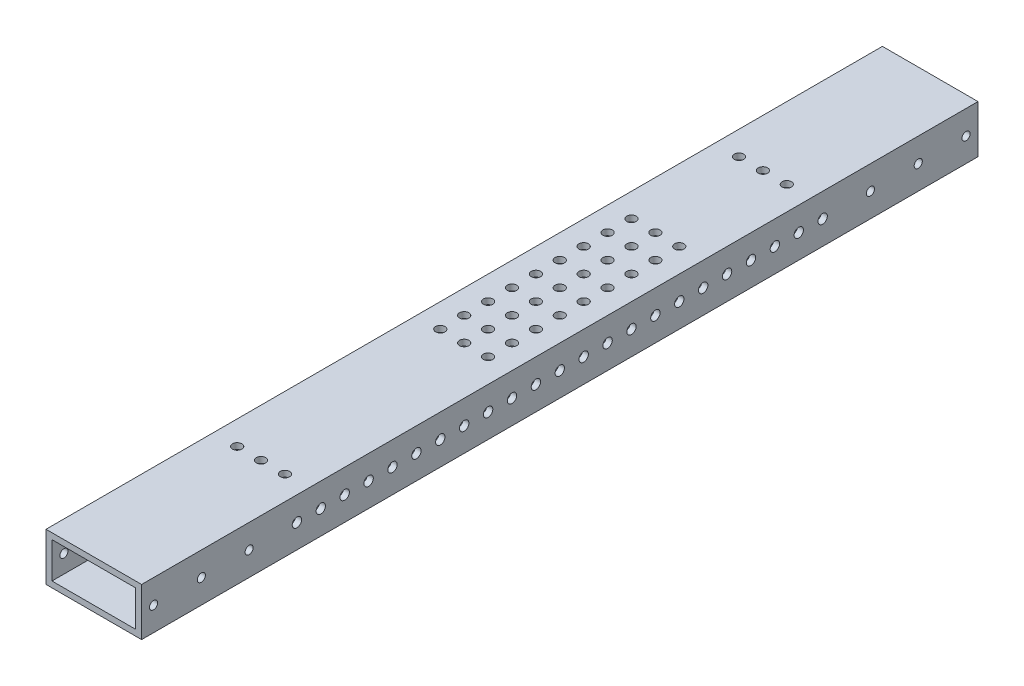
SolidWorks part; units mm, degrees
material "6061-T6 (SS)"
ref_plane "Front Plane" through (0, 0, 0) normal (0, 0, 1) x (1, 0, 0)
ref_plane "Top Plane" through (0, 0, 0) normal (0, 1, 0) x (1, 0, 0)
ref_plane "Right Plane" through (0, 0, 0) normal (1, 0, 0) x (0, 0, -1)
sketch "Sketch1" plane through (0, 0, 0) normal (0, 0, 1) x (1, 0, 0)
  line L0 (-22.225, 9.525) -> (22.225, 9.525)
  line L1 (-25.4, 12.7) -> (25.4, 12.7)
  line L2 (-25.4, 12.7) -> (-25.4, -12.7)
  line L3 (-25.4, -12.7) -> (25.4, -12.7)
  line L4 (25.4, 12.7) -> (25.4, -12.7)
  line L5 (22.225, 9.525) -> (22.225, -9.525)
  line L6 (-22.225, -9.525) -> (22.225, -9.525)
  line L7 (-22.225, 9.525) -> (-22.225, -9.525)
  line L8 (-25.4, 12.7) -> (25.4, -12.7) construction
  line L9 (25.4, 12.7) -> (-25.4, -12.7) construction
  point P5 (0, 0)
  dimension "D1" = 50.8
  dimension "D2" = 25.4
  dimension "D3" = 3.175
extrude "Boss-Extrude1" add sketch "Sketch1" along normal mid plane 444.5
sketch "Sketch3" plane through (25.4, 0, 0) normal (1, 0, 0) x (0, 0, -1)
  line L0 (-222.25, -12.7) -> (-222.25, 12.7) construction
  line L1 (-222.25, 12.7) -> (222.25, 12.7) construction
  line L2 (222.25, -12.7) -> (222.25, 12.7) construction
  circle A0 centre (-215.9, 0) radius 2.1527
  circle A1 centre (-190.5, 0) radius 2.1527
  circle A2 centre (-165.1, 0) radius 2.1527
  circle A3 centre (215.9, 0) radius 2.159
  circle A4 centre (190.5, 0) radius 2.159
  circle A5 centre (165.1, 0) radius 2.159
  dimension "D2" = 4.3053
  dimension "D9" = 4.318
  dimension "D1" = 6.35
  dimension "D3" = 12.7
  dimension "D4" = 31.75
  dimension "D5" = 12.7
  dimension "D6" = 57.15
  dimension "D7" = 12.7
  dimension "D8" = 6.35
  dimension "D10" = 12.7
  dimension "D11" = 31.75
  dimension "D12" = 57.15
  dimension "D13" = 12.7
  dimension "D14" = 12.7
extrude "Cut-Extrude2" cut sketch "Sketch3" against normal through all
sketch "Sketch4" plane through (25.4, 0, 0) normal (1, 0, 0) x (0, 0, -1)
  line L1 (-222.25, -12.7) -> (-222.25, 12.7) construction
  line L2 (-222.25, -12.7) -> (222.25, -12.7) construction
  circle A2 centre (-215.9, 0) radius 2.4892 construction
  circle A3 centre (-203.2, 0) radius 2.4892 construction
  circle A16 centre (-190.5, 0) radius 2.4892 construction
  circle A17 centre (-177.8, 0) radius 2.4892 construction
  circle A18 centre (-165.1, 0) radius 2.4892 construction
  circle A35 centre (-152.4, 0) radius 2.4892
  circle A36 centre (-139.7, 0) radius 2.4892
  circle A37 centre (-127, 0) radius 2.4892
  circle A38 centre (-114.3, 0) radius 2.4892
  circle A39 centre (-101.6, 0) radius 2.4892
  circle A40 centre (-88.9, 0) radius 2.4892
  circle A41 centre (-76.2, 0) radius 2.4892
  circle A42 centre (-63.5, 0) radius 2.4892
  circle A43 centre (-50.8, 0) radius 2.4892
  circle A44 centre (-38.1, 0) radius 2.4892
  circle A45 centre (-25.4, 0) radius 2.4892
  circle A46 centre (-12.7, 0) radius 2.4892
  circle A47 centre (0, 0) radius 2.4892
  circle A48 centre (12.7, 0) radius 2.4892
  circle A49 centre (25.4, 0) radius 2.4892
  circle A50 centre (38.1, 0) radius 2.4892
  circle A51 centre (50.8, 0) radius 2.4892
  circle A52 centre (63.5, 0) radius 2.4892
  circle A53 centre (76.2, 0) radius 2.4892
  circle A54 centre (88.9, 0) radius 2.4892
  circle A55 centre (101.6, 0) radius 2.4892
  circle A56 centre (114.3, 0) radius 2.4892
  circle A57 centre (127, 0) radius 2.4892
  circle A58 centre (139.7, 0) radius 2.4892
  circle A59 centre (152.4, 0) radius 2.4892
  circle A60 centre (165.1, 0) radius 2.4892 construction
  circle A61 centre (177.8, 0) radius 2.4892 construction
  circle A62 centre (190.5, 0) radius 2.4892 construction
  circle A63 centre (203.2, 0) radius 2.4892 construction
  dimension "D2" = 4.9784
  dimension "D1" = 6.35
  dimension "D3" = 12.7
  dimension "D4" = 12.7
  dimension "D5" = 34
extrude "Cut-Extrude3" cut sketch "Sketch4" against normal through all contours A36 | A37 | A38 | A39 | A40 | A41 | A42 | A43 | A44 | A45 | A46 | A47 | A48 | A49 | A50 | A51 | A52 | A53 | A54 | A55 | A56 | A57 | A58 region at (25.4, 0, 139.7) region at (25.4, 0, 127) region at (25.4, 0, 114.3) region at (25.4, 0, 101.6) region at (25.4, 0, 88.9) region at (25.4, 0, 76.2) region at (25.4, 0, 63.5) region at (25.4, 0, 50.8) region at (25.4, 0, 38.1) region at (25.4, 0, 25.4) region at (25.4, 0, 12.7) region at (25.4, 0, 0) region at (25.4, 0, -12.7) region at (25.4, 0, -25.4) region at (25.4, 0, -38.1) region at (25.4, 0, -50.8) region at (25.4, 0, -63.5) region at (25.4, 0, -76.2) region at (25.4, 0, -88.9) region at (25.4, 0, -101.6) region at (25.4, 0, -114.3) region at (25.4, 0, -127) region at (25.4, 0, -139.7)
sketch "Sketch5" plane through (0, -12.7, 0) normal (0, -1, 0) x (1, 0, 0)
  line L0 (-25.4, 0) -> (25.4, 0) construction
  line L4 (25.4, 222.25) -> (25.4, -222.25) construction
  line L5 (-25.4, 222.25) -> (-25.4, -222.25) construction
  line L6 (-25.4, 222.25) -> (25.4, 222.25) construction
  circle A0 centre (-12.7, 133.35) radius 2.4892
  circle A1 centre (0, 133.35) radius 2.4892
  circle A2 centre (12.7, 133.35) radius 2.4892
  circle A3 centre (12.7, -133.35) radius 2.4892
  circle A4 centre (0, -133.35) radius 2.4892
  circle A5 centre (-12.7, -133.35) radius 2.4892
  circle A6 centre (-12.7, 25.4) radius 2.4892
  circle A7 centre (0, 25.4) radius 2.4892
  circle A8 centre (12.7, 25.4) radius 2.4892
  circle A9 centre (12.7, 12.7) radius 2.4892
  circle A10 centre (0, 12.7) radius 2.4892
  circle A11 centre (-12.7, 12.7) radius 2.4892
  circle A12 centre (12.7, 0) radius 2.4892
  circle A13 centre (0, 0) radius 2.4892
  circle A14 centre (-12.7, 0) radius 2.4892
  circle A15 centre (12.7, -12.7) radius 2.4892
  circle A16 centre (0, -12.7) radius 2.4892
  circle A17 centre (-12.7, -12.7) radius 2.4892
  circle A18 centre (12.7, -25.4) radius 2.4892
  circle A19 centre (0, -25.4) radius 2.4892
  circle A20 centre (-12.7, -25.4) radius 2.4892
  circle A21 centre (12.7, -38.1) radius 2.4892
  circle A22 centre (0, -38.1) radius 2.4892
  circle A23 centre (-12.7, -38.1) radius 2.4892
  circle A24 centre (12.7, -50.8) radius 2.4892
  circle A25 centre (0, -50.8) radius 2.4892
  circle A26 centre (-12.7, -50.8) radius 2.4892
  circle A27 centre (12.7, -63.5) radius 2.4892
  circle A28 centre (0, -63.5) radius 2.4892
  circle A29 centre (-12.7, -63.5) radius 2.4892
  circle A30 centre (12.7, -76.2) radius 2.4892
  circle A31 centre (0, -76.2) radius 2.4892
  circle A32 centre (-12.7, -76.2) radius 2.4892
  dimension "D1" = 4.9784
  dimension "D3" = 12.7
  dimension "D2" = 88.9
  dimension "D5" = 12.7
  dimension "D4" = 12.7
  dimension "D6" = 107.95
  dimension "D8" = 12.7
  dimension "D7" = 9
extrude "Cut-Extrude4" cut sketch "Sketch5" against normal through all
